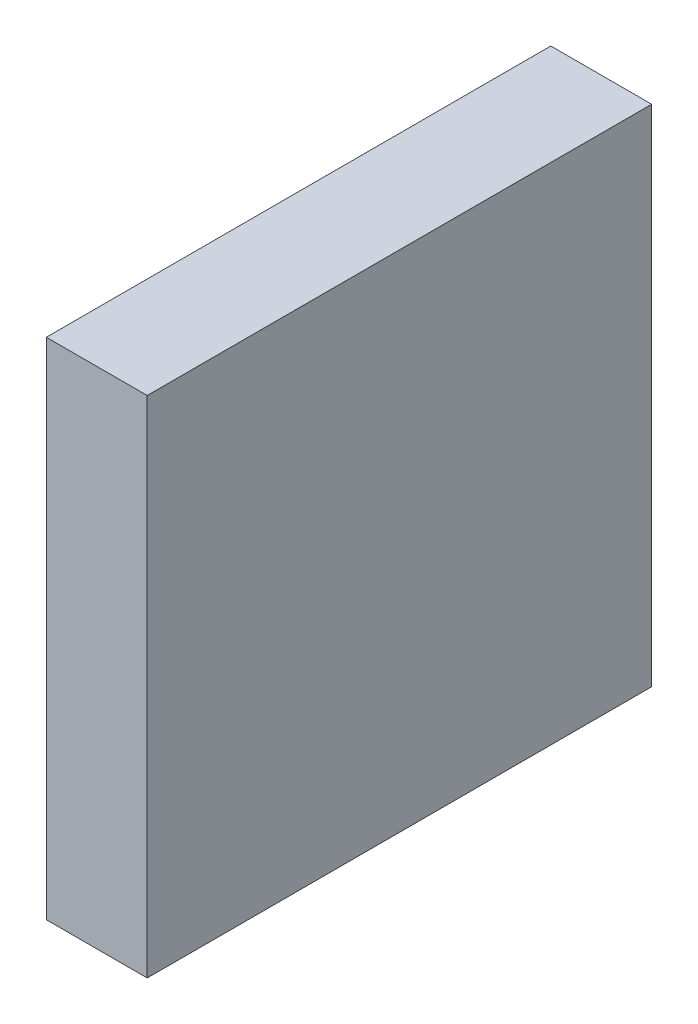
SolidWorks part; units mm, degrees
ref_plane "前视基准面" through (0, 0, 0) normal (0, 0, 1) x (1, 0, 0)
ref_plane "上视基准面" through (0, 0, 0) normal (0, 1, 0) x (1, 0, 0)
ref_plane "右视基准面" through (0, 0, 0) normal (1, 0, 0) x (0, 0, -1)
ref_plane "LEDTop" through (0, 0, 0) normal (0, 1, 0) x (1, 0, 0)
ref_plane "CenterV" through (0, 0, 0) normal (1, 0, 0) x (0, 0, -1)
ref_plane "CenterH" through (0, 0, 0) normal (0, 0, 1) x (1, 0, 0)
sketch "Circle" plane through (0, 0, 0) normal (0, 1, 0) x (1, 0, 0)
  line L0 (0, 0) -> (-200, 0) construction
  dimension "R" = 200
ref_axis "CenterAxis" through (-200, 0, 0) along (0, 1, 0)
sketch "SRectangle" plane through (0, 0, 0) normal (0, 1, 0) x (1, 0, 0)
  line L1 (-0.5, -2.5) -> (0.5, -2.5)
  line L2 (-0.5, -2.5) -> (-0.5, 2.5)
  line L3 (-0.5, 2.5) -> (0.5, 2.5)
  line L4 (0.5, -2.5) -> (0.5, 2.5)
  line L5 (-0.5, -2.5) -> (0.5, 2.5) construction
  line L6 (-0.5, 2.5) -> (0.5, -2.5) construction
  point P0 (0, 0)
  dimension "D1" = 1
  dimension "D2" = 5
extrude "FRectangle" add sketch "SRectangle" against normal blind 5
sketch "RectangleCut" plane through (0, 0, 0) normal (0, 1, 0) x (1, 0, 0)
  line L4 (-0.5, -2.5) -> (0.5, -2.5)
  line L5 (0.5, -2.5) -> (0.5, 2.5)
  line L6 (0.5, 2.5) -> (-0.5, 2.5)
  line L7 (-0.5, 2.5) -> (-0.5, -2.5)
  line L8 (-0.5, -2.5) -> (0.5, -2.5)
  line L9 (0.5, -2.5) -> (0.5, 2.5)
  line L10 (0.5, 2.5) -> (-0.5, 2.5)
  line L11 (-0.5, 2.5) -> (-0.5, -2.5)
  dimension "D1" = 0
sketch "SRound" [suppressed] plane through (0, 0, 0) normal (0, 1, 0) x (1, 0, 0)
  circle A0 centre (0, 0) radius 1
  dimension "D1" = 2
extrude "FRound" [suppressed] add sketch "SRound" against normal blind 5
sketch "RoundCut" [suppressed] plane through (0, 0, 0) normal (0, 1, 0) x (1, 0, 0)
  circle A1 centre (0, 0) radius 1
  circle A2 centre (0, 0) radius 1
  dimension "D1" = 0
equation "\"LedH\"= 5"
equation "\"D1@FRectangle\"=\"LedH\""
equation "\"D1@FRound\"=\"LedH\""
